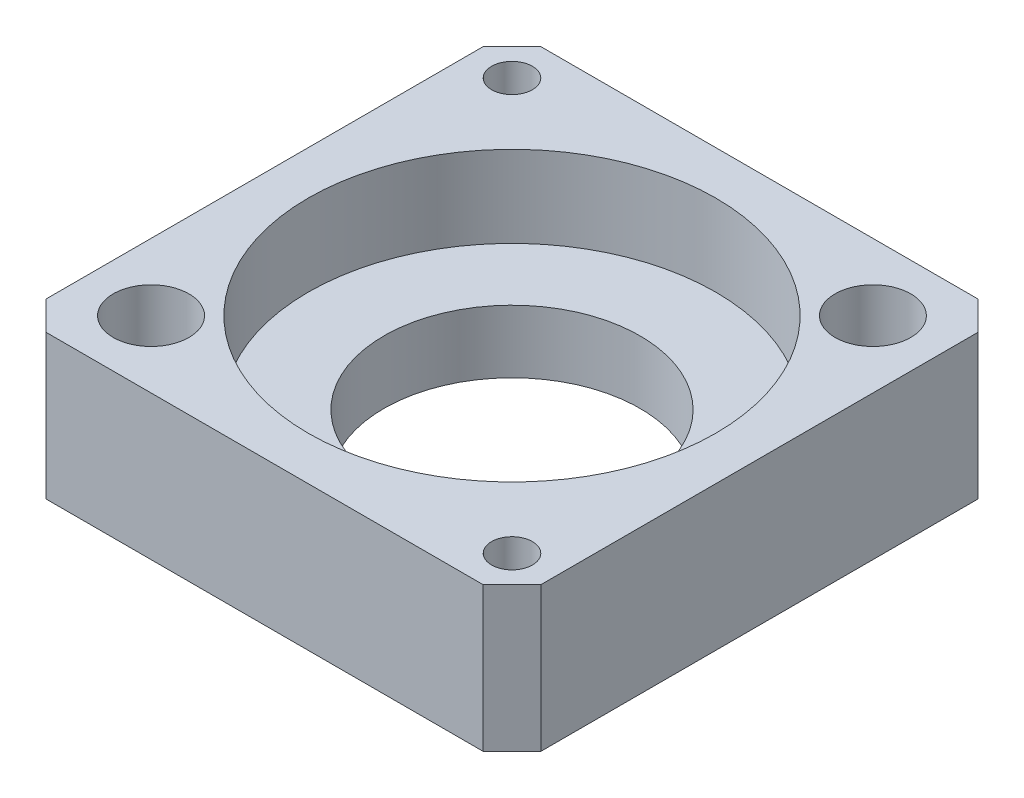
SolidWorks part; units mm, degrees
ref_plane "前视基准面" through (0, 0, 0) normal (0, 0, 1) x (1, 0, 0)
ref_plane "上视基准面" through (0, 0, 0) normal (0, 1, 0) x (1, 0, 0)
ref_plane "右视基准面" through (0, 0, 0) normal (1, 0, 0) x (0, 0, -1)
sketch "草图1" plane through (0, 0, 0) normal (0, 1, 0) x (1, 0, 0)
  line L0 (0, 2.4749) -> (2.4749, 0)
  line L1 (0, 0) -> (42.5, 0)
  line L2 (0, 0) -> (0, 42.5)
  line L3 (0, 42.5) -> (42.5, 42.5)
  line L4 (42.5, 0) -> (42.5, 42.5)
  line L5 (1.2374, 1.2374) -> (42.5, 42.5) construction
  line L6 (0, 21.25) -> (42.5, 21.25) construction
  line L7 (2.4749, 42.5) -> (0, 40.0251)
  line L8 (42.5, 40.0251) -> (40.0251, 42.5)
  line L9 (40.0251, 0) -> (42.5, 2.4749)
  point P8 (21.25, 21.25)
  dimension "D1" = 42.5
  dimension "D2" = 3.5
  dimension "D3" = 4
extrude "凸台-拉伸1" add sketch "草图1" along normal blind 12.4 contours L1 L9 L4 L8 L3 L7 L2 L0 region at (21.25, 0, -21.25)
sketch "草图2" plane through (0, 12.4, 0) normal (0, 1, 0) x (1, 0, 0)
  line L0 (0, 21.25) -> (42.5, 21.25) construction
  line L1 (0, 2.4749) -> (0, 40.0251) construction
  line L2 (42.5, 2.4749) -> (42.5, 40.0251) construction
  circle A0 centre (21.25, 21.25) radius 17.5
  dimension "D1" = 35
extrude "切除-拉伸1" cut sketch "草图2" against normal blind 7
sketch "草图3" plane through (0, 5.4, 0) normal (0, 1, 0) x (1, 0, 0)
  circle A0 centre (21.25, 21.25) radius 11
  dimension "D1" = 22
extrude "切除-拉伸2" cut sketch "草图3" against normal through all
sketch "草图4" plane through (0, 12.4, 0) normal (0, 1, 0) x (1, 0, 0)
  line L0 (21.25, 21.25) -> (1.2374, 41.2626) construction
  line L1 (2.4749, 42.5) -> (0, 40.0251) construction
  line L2 (21.25, 21.25) -> (38.9277, 3.5723) construction
  line L4 (5.75, 5.75) -> (36.75, 5.75) construction
  line L5 (5.75, 5.75) -> (5.75, 36.75) construction
  line L6 (5.75, 36.75) -> (36.75, 36.75) construction
  line L7 (36.75, 5.75) -> (36.75, 36.75) construction
  line L8 (5.75, 5.75) -> (36.75, 36.75) construction
  line L9 (5.75, 36.75) -> (36.75, 5.75) construction
  circle A0 centre (21.25, 21.25) radius 25 construction
  circle A1 centre (3.5723, 38.9277) radius 1.75
  circle A2 centre (38.9277, 3.5723) radius 1.75
  circle A3 centre (36.75, 36.75) radius 3.25
  circle A4 centre (5.75, 5.75) radius 3.25
  circle A5 centre (5.75, 5.75) radius 1.525
  circle A6 centre (36.75, 36.75) radius 1.525
  dimension "D1" = 50
  dimension "D2" = 3.5
  dimension "D5" = 6.5
  dimension "D6" = 3.05
  dimension "D4" = 31
  dimension "D3" = 2
extrude "切除-拉伸3" cut sketch "草图4" against normal blind 10 contours A4 | A3 | A5 | A6 region at (33.5919, 12.4, -36.75) region at (2.5919, 12.4, -5.75) region at (5.75, 12.4, -5.75) region at (36.75, 12.4, -36.75)
extrude "切除-拉伸4" cut sketch "草图4<3>" against normal through all contours A5 | A2 | A6 | A1 region at (3.5723, 12.4, -38.9277) region at (38.9277, 12.4, -3.5723) region at (5.75, 12.4, -5.75) region at (36.75, 12.4, -36.75)
sketch "草图4<3>" plane through (0, 12.4, 0) normal (0, 1, 0) x (1, 0, 0) same geometry as "草图4"
